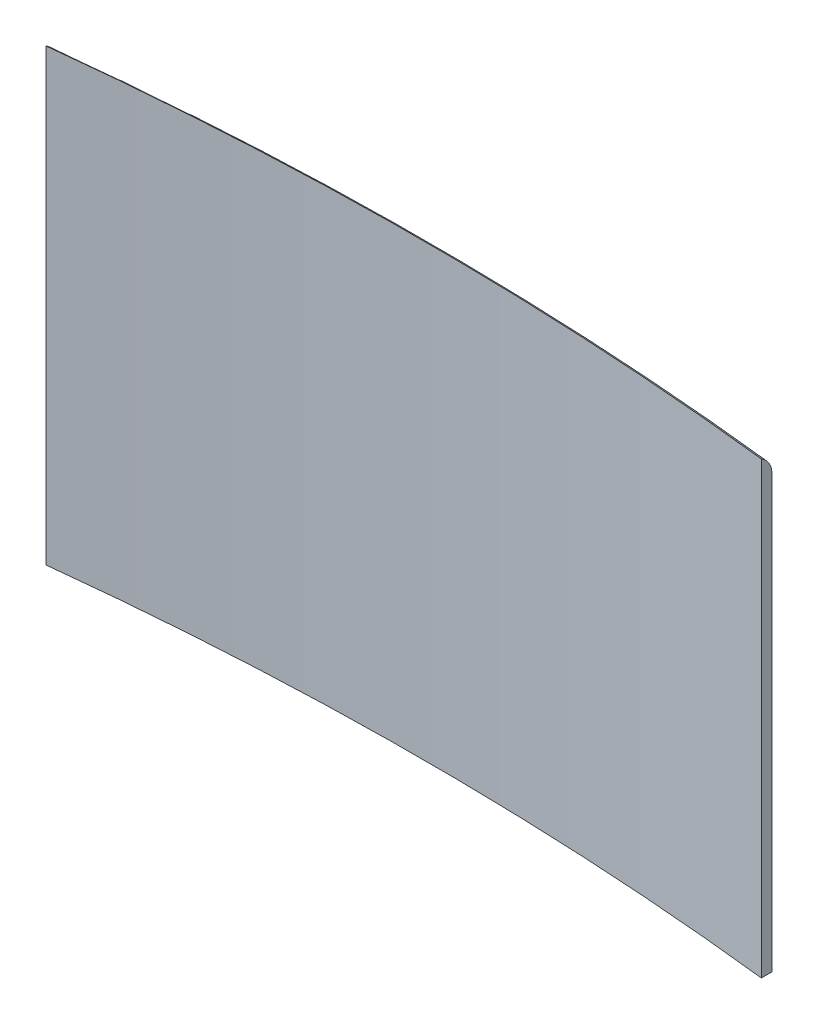
SolidWorks part; units mm, degrees
ref_plane "Front Plane" through (0, 0, 0) normal (0, 0, 1) x (1, 0, 0)
ref_plane "Top Plane" through (0, 0, 0) normal (0, 1, 0) x (1, 0, 0)
ref_plane "Right Plane" through (0, 0, 0) normal (1, 0, 0) x (0, 0, -1)
sketch "Sketch1" plane through (0, 0, 0) normal (0, 1, 0) x (1, 0, 0)
  line L0 (0, 0) -> (0, 1.01)
  line L1 (-68, 1.01) -> (-68, 0)
  line L2 (0, 0) -> (-68, 0) construction
  arc A0 (0, 0) -> (-68, 0) centre (-34, -302.0927) ccw
  arc A1 (0, 1.01) -> (-68, 1.01) centre (-34, -302.0927) ccw
  dimension "D2" = 68
  dimension "D3" = 304
  dimension "D1" = 305.0037
extrude "Boss-Extrude1" add sketch "Sketch1" along normal blind 42.73
fillet "Fillet1" radius 2 1 edges at (-34, 42.73, -2.911)
